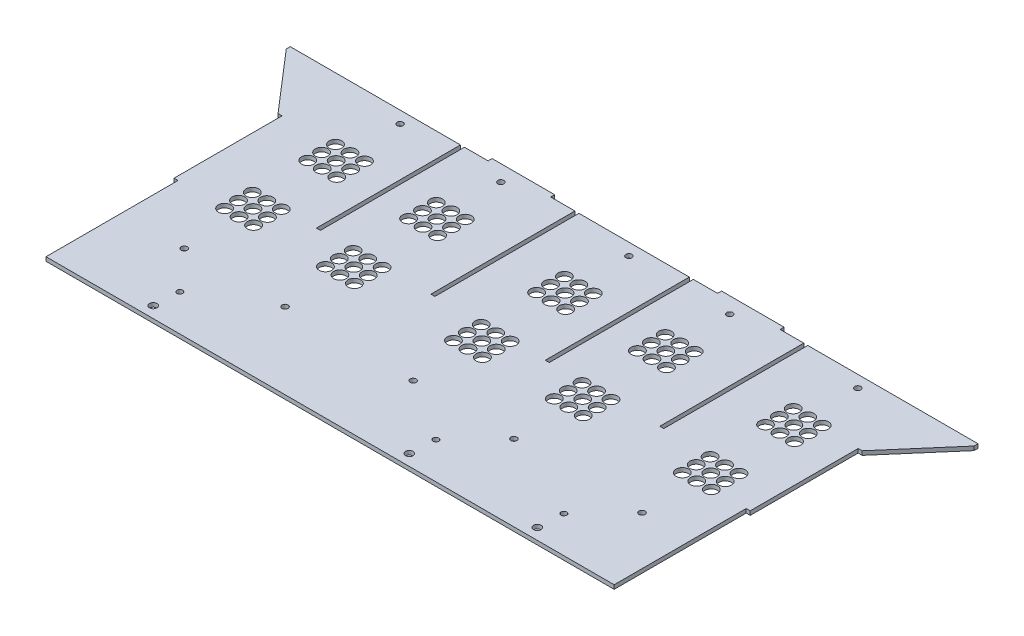
SolidWorks part; units mm, degrees
material "6061-T6 (SS)"
ref_plane "X-Y Datum" through (0, 0, 0) normal (0, 0, 1) x (1, 0, 0)
ref_plane "X-Z Datum" through (0, 0, 0) normal (0, 1, 0) x (1, 0, 0)
ref_plane "Y-Z Datum" through (0, 0, 0) normal (1, 0, 0) x (0, 0, -1)
sketch "Sketch1" plane through (0, 0, 0) normal (0, 0, 1) x (1, 0, 0)
  line L1 (-228.601, -1.5875) -> (228.601, -1.5875)
  line L2 (-228.601, -1.5875) -> (-228.601, 1.5875)
  line L3 (-228.601, 1.5875) -> (228.601, 1.5875)
  line L4 (228.601, -1.5875) -> (228.601, 1.5875)
  line L5 (-228.601, -1.5875) -> (228.601, 1.5875) construction
  line L6 (-228.601, 1.5875) -> (228.601, -1.5875) construction
  point P0 (0, 0)
  dimension "D1" = 3.175
  dimension "D2" = 457.202
extrude "Boss-Extrude1" add sketch "Sketch1" along normal blind 241.2744
sketch "Sketch2" plane through (0, 1.5875, 0) normal (0, 1, 0) x (1, 0, 0)
  line L0 (228.601, 0) -> (225.426, 0)
  line L1 (228.601, 0) -> (-228.601, 0) construction
  line L2 (225.426, 0) -> (137.796, 0)
  line L3 (137.796, 0) -> (134.621, 0)
  line L10 (134.621, 0) -> (137.796, 0)
  line L11 (134.621, 0) -> (134.621, -114.3)
  line L12 (134.621, -114.3) -> (137.796, -114.3)
  line L13 (137.796, 0) -> (137.796, -114.3)
  line M2 (228.601, 0) -> (-228.601, 0)
  dimension "D1" = 87.63
  dimension "D2" = 3.175
  dimension "D3" = 114.3
  dimension "D4" = 3.175
extrude "Cut-Extrude1" cut sketch "Sketch2" against normal through all contours L13 L11 L12 M2 region at (136.2085, 1.5875, 57.15)
pattern_linear "LPattern1" count 4 spacing 90.807 along (-1, 0, 0) of "Cut-Extrude1"
sketch "Sketch4" plane through (0, -1.5875, 0) normal (0, -1, 0) x (1, 0, 0)
  line L0 (-228.601, 0) -> (-272.876, 0)
  line L2 (-228.601, 241.2744) -> (-228.601, 0) construction
  line L3 (-228.601, 50.8) -> (-228.601, 0)
  line L4 (-272.876, 0) -> (-272.876, 3.175)
  line L6 (-228.601, 50.8) -> (-231.776, 50.8)
  line L7 (-231.776, 50.8) -> (-272.876, 3.175)
  dimension "D1" = 44.275
  dimension "D2" = 50.8
  dimension "D3" = 3.175
  dimension "D4" = 3.175
extrude "Boss-Extrude3" add sketch "Sketch4" against normal blind 3.175
mirror "Mirror1" about plane through (0, 0, 0) normal (1, 0, 0) of "Boss-Extrude3"
sketch "Sketch5" plane through (0, -1.5875, 0) normal (0, -1, 0) x (1, 0, 0)
  line L1 (-228.601, 241.2744) -> (-225.426, 241.2744)
  line L2 (-228.601, 241.2744) -> (-228.601, 136.4994)
  line L3 (-228.601, 136.4994) -> (-225.426, 136.4994)
  line L4 (-225.426, 241.2744) -> (-225.426, 136.4994)
  dimension "D1" = 3.175
  dimension "D2" = 104.775
extrude "Cut-Extrude2" cut sketch "Sketch5" against normal blind 3.175
mirror "Mirror2" about plane through (0, 0, 0) normal (1, 0, 0) of "Cut-Extrude2"
sketch "Sketch37" plane through (0, 1.5875, 0) normal (0, 1, 0) x (1, 0, 0)
  line L0 (-149.226, -241.2744) -> (-149.226, -232.3844) construction
  line L1 (225.426, -241.2744) -> (-225.426, -241.2744) construction
  line L2 (-225.426, -136.4994) -> (-225.426, -241.2744) construction
  circle A0 centre (-149.226, -232.3844) radius 3
  dimension "D1" = 8.89
  dimension "D3" = 6
  dimension "D2" = 76.2
extrude "Cut-Extrude12" cut sketch "Sketch37" against normal blind 3.175
pattern_linear "LPattern31" count 4 spacing 101.6 along (1, 0, 0) skipping (1, 0) of "Cut-Extrude12"
sketch "Sketch51" plane through (0, 1.5875, 0) normal (0, 1, 0) x (1, 0, 0)
  point P0 (-176.2216, -180.775)
  point P1 (-176.2216, -9.525)
  point P3 (-96.2064, -9.525)
  point P5 (-96.2064, -180.775)
hole_wizard "M4 Clearance Hole1" positions "Sketch55" profile "Sketch53" hole size "M4" standard "ANSI Metric" end condition up to next
sketch "Sketch55" plane through (0, 1.5875, 0) normal (0, 1, 0) x (1, 0, 0)
  point P0 (-176.2216, -180.775)
  point P3 (-176.2216, -9.525)
sketch "Sketch53" plane through (-176.2216, 1.5875, 180.775) normal (1, 0, 0) x (0, 0, 1)
  line L0 (0, 0) -> (0, 3.175)
  line L1 (0, 3.175) -> (2.4, 3.175)
  line L2 (2.4, 3.175) -> (2.4, 0)
  line L5 (2.4, 0) -> (0, 0)
  line L11 (0, -6.35) -> (0, 107.95) construction
  dimension "Thru Hole Dia." = 4.8
  dimension "Thru Hole Depth" = 3.175
hole_wizard "M4 Clearance Hole2" positions "Sketch58" profile "Sketch57" hole size "M4" standard "ANSI Metric" end condition up to next
sketch "Sketch58" plane through (0, 1.5875, 0) normal (0, 1, 0) x (1, 0, 0)
  point P0 (-96.2064, -180.775)
  point P3 (-96.2064, -9.525)
sketch "Sketch57" plane through (-96.2064, 1.5875, 180.775) normal (1, 0, 0) x (0, 0, 1)
  line L0 (0, 0) -> (0, 3.175)
  line L1 (0, 3.175) -> (2.4, 3.175)
  line L2 (2.4, 3.175) -> (2.4, 0)
  line L5 (2.4, 0) -> (0, 0)
  line L11 (0, -6.35) -> (0, 107.95) construction
  dimension "Thru Hole Dia." = 4.8
  dimension "Thru Hole Depth" = 3.175
pattern_linear "LPattern32" count 3 spacing 181.614 along (1, 0, 0) of "M4 Clearance Hole1"
pattern_linear "LPattern33" count 2 spacing 181.614 along (1, 0, 0) of "M4 Clearance Hole2"
sketch "Sketch59" plane through (0, 1.5875, 0) normal (0, 1, 0) x (1, 0, 0)
  circle A0 centre (-187.7216, -115.2567) radius 5 construction
  circle A1 centre (-176.2216, -115.2567) radius 5 construction
  circle A2 centre (-164.7216, -115.2567) radius 5 construction
  circle A3 centre (-164.7216, -126.2567) radius 5 construction
  circle A4 centre (-176.2216, -126.2567) radius 5 construction
  circle A5 centre (-187.7216, -126.2567) radius 5 construction
  circle A6 centre (-187.7216, -137.2567) radius 5 construction
  circle A7 centre (-176.2216, -137.2567) radius 5 construction
  circle A8 centre (-164.7216, -137.2567) radius 5 construction
  circle A9 centre (-187.7216, -115.2567) radius 5
  circle A10 centre (-176.2216, -115.2567) radius 5
  circle A11 centre (-164.7216, -115.2567) radius 5
  circle A12 centre (-164.7216, -126.2567) radius 5
  circle A13 centre (-176.2216, -126.2567) radius 5
  circle A14 centre (-187.7216, -126.2567) radius 5
  circle A15 centre (-187.7216, -137.2567) radius 5
  circle A16 centre (-176.2216, -137.2567) radius 5
  circle A17 centre (-164.7216, -137.2567) radius 5
  circle A18 centre (-187.7216, -71.2567) radius 5 construction
  circle A19 centre (-176.2216, -71.2567) radius 5 construction
  circle A20 centre (-164.7216, -71.2567) radius 5 construction
  circle A21 centre (-176.2216, -60.2567) radius 5 construction
  circle A22 centre (-187.7216, -60.2567) radius 5 construction
  circle A23 centre (-187.7216, -49.2567) radius 5 construction
  circle A24 centre (-176.2216, -49.2567) radius 5 construction
  circle A25 centre (-164.7216, -49.2567) radius 5 construction
  circle A26 centre (-164.7216, -60.2567) radius 5 construction
  circle A27 centre (-187.7216, -71.2567) radius 5
  circle A28 centre (-176.2216, -71.2567) radius 5
  circle A29 centre (-164.7216, -71.2567) radius 5
  circle A30 centre (-176.2216, -60.2567) radius 5
  circle A31 centre (-187.7216, -60.2567) radius 5
  circle A32 centre (-187.7216, -49.2567) radius 5
  circle A33 centre (-176.2216, -49.2567) radius 5
  circle A34 centre (-164.7216, -49.2567) radius 5
  circle A35 centre (-164.7216, -60.2567) radius 5
  circle A36 centre (-107.7064, -126.2567) radius 5 construction
  circle A37 centre (-107.7064, -115.2567) radius 5 construction
  circle A38 centre (-107.7064, -137.2567) radius 5 construction
  circle A39 centre (-96.2064, -137.2567) radius 5 construction
  circle A40 centre (-96.2064, -126.2567) radius 5 construction
  circle A41 centre (-96.2064, -115.2567) radius 5 construction
  circle A42 centre (-84.7064, -115.2567) radius 5 construction
  circle A43 centre (-84.7064, -126.2567) radius 5 construction
  circle A44 centre (-84.7064, -137.2567) radius 5 construction
  circle A45 centre (-107.7064, -126.2567) radius 5
  circle A46 centre (-107.7064, -115.2567) radius 5
  circle A47 centre (-107.7064, -137.2567) radius 5
  circle A48 centre (-96.2064, -137.2567) radius 5
  circle A49 centre (-96.2064, -126.2567) radius 5
  circle A50 centre (-96.2064, -115.2567) radius 5
  circle A51 centre (-84.7064, -115.2567) radius 5
  circle A52 centre (-84.7064, -126.2567) radius 5
  circle A53 centre (-84.7064, -137.2567) radius 5
  circle A54 centre (-84.7064, -49.2567) radius 5 construction
  circle A55 centre (-96.2064, -49.2567) radius 5 construction
  circle A56 centre (-107.7064, -49.2567) radius 5 construction
  circle A57 centre (-107.7064, -60.2567) radius 5 construction
  circle A58 centre (-107.7064, -71.2567) radius 5 construction
  circle A59 centre (-96.2064, -71.2567) radius 5 construction
  circle A60 centre (-96.2064, -60.2567) radius 5 construction
  circle A61 centre (-84.7064, -60.2567) radius 5 construction
  circle A62 centre (-84.7064, -71.2567) radius 5 construction
  circle A63 centre (-84.7064, -49.2567) radius 5
  circle A64 centre (-96.2064, -49.2567) radius 5
  circle A65 centre (-107.7064, -49.2567) radius 5
  circle A66 centre (-107.7064, -60.2567) radius 5
  circle A67 centre (-107.7064, -71.2567) radius 5
  circle A68 centre (-96.2064, -71.2567) radius 5
  circle A69 centre (-96.2064, -60.2567) radius 5
  circle A70 centre (-84.7064, -60.2567) radius 5
  circle A71 centre (-84.7064, -71.2567) radius 5
extrude "Cut-Extrude13" cut sketch "Sketch59" against normal through all contours A34 | A33 | A32 | A31 | A35 | A29 | A28 | A27 | A15 | A16 | A17 | A12 | A13 | A14 | A11 | A10 | A9 | A30 region at (-187.7216, 1.5875, 115.2567) region at (-176.2216, 1.5875, 115.2567) region at (-164.7216, 1.5875, 115.2567) region at (-164.7216, 1.5875, 126.2567) region at (-176.2216, 1.5875, 126.2567) region at (-187.7216, 1.5875, 126.2567) region at (-187.7216, 1.5875, 137.2567) region at (-176.2216, 1.5875, 137.2567) region at (-164.7216, 1.5875, 137.2567) region at (-187.7216, 1.5875, 71.2567) region at (-176.2216, 1.5875, 71.2567) region at (-164.7216, 1.5875, 71.2567) region at (-187.7216, 1.5875, 60.2567) region at (-187.7216, 1.5875, 49.2567) region at (-176.2216, 1.5875, 49.2567) region at (-164.7216, 1.5875, 49.2567) region at (-164.7216, 1.5875, 60.2567)
pattern_linear "LPattern34" count 3 spacing 181.614 along (1, 0, 0) of "Cut-Extrude13"
sketch "Sketch60" plane through (0, 1.5875, 0) normal (0, 1, 0) x (1, 0, 0)
  circle A1 centre (-164.7216, -137.2567) radius 5
  circle A2 centre (-164.7216, -137.2567) radius 5
  circle A3 centre (-176.2216, -137.2567) radius 5
  circle A4 centre (-176.2216, -137.2567) radius 5
  circle A5 centre (-187.7216, -137.2567) radius 5
  circle A6 centre (-187.7216, -137.2567) radius 5
  circle A7 centre (-187.7216, -126.2567) radius 5
  circle A8 centre (-187.7216, -126.2567) radius 5
  circle A9 centre (-176.2216, -126.2567) radius 5
  circle A10 centre (-176.2216, -126.2567) radius 5
  circle A11 centre (-164.7216, -126.2567) radius 5
  circle A12 centre (-164.7216, -126.2567) radius 5
  circle A13 centre (-164.7216, -115.2567) radius 5
  circle A14 centre (-164.7216, -115.2567) radius 5
  circle A15 centre (-176.2216, -115.2567) radius 5
  circle A16 centre (-176.2216, -115.2567) radius 5
  circle A17 centre (-187.7216, -115.2567) radius 5
  circle A18 centre (-187.7216, -115.2567) radius 5
  circle A19 centre (-164.7216, -71.2567) radius 5
  circle A20 centre (-164.7216, -71.2567) radius 5
  circle A21 centre (-176.2216, -71.2567) radius 5
  circle A22 centre (-176.2216, -71.2567) radius 5
  circle A23 centre (-187.7216, -71.2567) radius 5
  circle A24 centre (-187.7216, -71.2567) radius 5
  circle A25 centre (-164.7216, -60.2567) radius 5
  circle A26 centre (-164.7216, -60.2567) radius 5
  circle A27 centre (-164.7216, -49.2567) radius 5
  circle A28 centre (-164.7216, -49.2567) radius 5
  circle A29 centre (-176.2216, -49.2567) radius 5
  circle A30 centre (-176.2216, -49.2567) radius 5
  circle A31 centre (-187.7216, -49.2567) radius 5
  circle A32 centre (-187.7216, -49.2567) radius 5
  circle A33 centre (-187.7216, -60.2567) radius 5
  circle A34 centre (-187.7216, -60.2567) radius 5
  circle A35 centre (-176.2216, -60.2567) radius 5
  circle A36 centre (-176.2216, -60.2567) radius 5
  circle A37 centre (-84.7064, -126.2567) radius 5
  circle A38 centre (-84.7064, -126.2567) radius 5
  circle A39 centre (-84.7064, -115.2567) radius 5
  circle A40 centre (-84.7064, -115.2567) radius 5
  circle A41 centre (-96.2064, -115.2567) radius 5
  circle A42 centre (-96.2064, -115.2567) radius 5
  circle A43 centre (-96.2064, -126.2567) radius 5
  circle A44 centre (-96.2064, -126.2567) radius 5
  circle A45 centre (-96.2064, -137.2567) radius 5
  circle A46 centre (-96.2064, -137.2567) radius 5
  circle A47 centre (-107.7064, -137.2567) radius 5
  circle A48 centre (-107.7064, -137.2567) radius 5
  circle A49 centre (-107.7064, -115.2567) radius 5
  circle A50 centre (-107.7064, -115.2567) radius 5
  circle A51 centre (-107.7064, -126.2567) radius 5
  circle A52 centre (-107.7064, -126.2567) radius 5
  circle A53 centre (-84.7064, -137.2567) radius 5
  circle A54 centre (-84.7064, -137.2567) radius 5
  circle A55 centre (-84.7064, -71.2567) radius 5
  circle A56 centre (-84.7064, -71.2567) radius 5
  circle A57 centre (-84.7064, -60.2567) radius 5
  circle A58 centre (-84.7064, -60.2567) radius 5
  circle A59 centre (-96.2064, -60.2567) radius 5
  circle A60 centre (-96.2064, -60.2567) radius 5
  circle A61 centre (-96.2064, -71.2567) radius 5
  circle A62 centre (-96.2064, -71.2567) radius 5
  circle A63 centre (-107.7064, -71.2567) radius 5
  circle A64 centre (-107.7064, -71.2567) radius 5
  circle A65 centre (-107.7064, -60.2567) radius 5
  circle A66 centre (-107.7064, -60.2567) radius 5
  circle A67 centre (-107.7064, -49.2567) radius 5
  circle A68 centre (-107.7064, -49.2567) radius 5
  circle A69 centre (-96.2064, -49.2567) radius 5
  circle A70 centre (-96.2064, -49.2567) radius 5
  circle A71 centre (-84.7064, -49.2567) radius 5
  circle A72 centre (-84.7064, -49.2567) radius 5
  dimension "D1" = 0
  dimension "D2" = 0
  dimension "D3" = 0
  dimension "D4" = 0
  dimension "D5" = 0
  dimension "D6" = 0
  dimension "D7" = 0
  dimension "D8" = 0
  dimension "D9" = 0
  dimension "D10" = 0
  dimension "D11" = 0
  dimension "D12" = 0
  dimension "D13" = 0
  dimension "D14" = 0
  dimension "D15" = 0
  dimension "D16" = 0
  dimension "D17" = 0
  dimension "D18" = 0
  dimension "D19" = 0
  dimension "D20" = 0
  dimension "D21" = 0
  dimension "D22" = 0
  dimension "D23" = 0
  dimension "D24" = 0
  dimension "D25" = 0
  dimension "D26" = 0
  dimension "D27" = 0
  dimension "D28" = 0
  dimension "D29" = 0
  dimension "D30" = 0
  dimension "D31" = 0
  dimension "D32" = 0
  dimension "D33" = 0
  dimension "D34" = 0
  dimension "D35" = 0
  dimension "D36" = 0
extrude "Cut-Extrude14" cut sketch "Sketch60" against normal through all contours A48 | A46 | A54 | A38 | A52 | A44 | A40 | A42 | A50 | A72 | A58 | A60 | A70 | A68 | A64 | A66 | A62 | A56
pattern_linear "LPattern35" count 2 spacing 181.614 along (1, 0, 0) of "Cut-Extrude14"
sketch "Sketch61" plane through (0, 1.5875, 0) normal (0, 1, 0) x (1, 0, 0)
  point P0 (-148.21, -212.285)
  point P1 (54.99, -212.285)
  point P3 (156.59, -212.285)
hole_wizard "M4 Clearance Hole3" positions "Sketch61" profile "Sketch62" hole size "M4" standard "ANSI Metric" end condition through all
sketch "Sketch62" plane through (-148.21, 1.5875, 212.285) normal (1, 0, 0) x (0, 0, 1)
  line L0 (0, 0) -> (0, 3.175)
  line L1 (0, 3.175) -> (2.25, 3.175)
  line L2 (2.25, 3.175) -> (2.25, 0)
  line L5 (2.25, 0) -> (0, 0)
  line L11 (0, -6.35) -> (0, 107.95) construction
  dimension "Thru Hole Dia." = 4.5
  dimension "Thru Hole Depth" = 3.175
sketch "Sketch63" plane through (0, 0, 0) normal (0, 0, -1) x (-1, 0, 0)
  line L0 (-66.1907, 1.5875) -> (-66.1907, -1.5875) construction
  line L1 (-115.8495, 1.5875) -> (-115.8495, -1.5875) construction
  line L2 (-115.8495, -1.5875) -> (-66.1907, -1.5875) construction
  line L3 (-66.1907, 1.5875) -> (-66.1907, -1.5875)
  line L4 (-115.8495, 1.5875) -> (-115.8495, -1.5875)
  line L5 (-115.8495, -1.5875) -> (-66.1907, -1.5875)
  line L6 (-228.1875, 1.7703) -> (228.1875, 1.7703) construction
  line L7 (-228.1875, 1.7703) -> (228.1875, 1.7703)
  line L8 (115.8495, 1.5875) -> (115.8495, -1.5875) construction
  line L9 (66.1907, 1.5875) -> (66.1907, -1.5875) construction
  line L10 (115.8495, -1.5875) -> (66.1907, -1.5875) construction
  line L11 (115.8495, 1.5875) -> (115.8495, -1.5875)
  line L12 (66.1907, 1.5875) -> (66.1907, -1.5875)
  line L13 (115.8495, -1.5875) -> (66.1907, -1.5875)
  line L14 (46.993, 1.5875) -> (134.625, 1.5875) construction
  line L15 (46.993, 1.5875) -> (134.625, 1.5875)
  line M1 (-134.621, -1.5875) -> (-46.989, -1.5875)
  line M3 (-46.989, 1.5875) -> (-134.621, 1.5875)
extrude "Boss-Extrude4" add sketch "Sketch63" along normal blind 3.175 contours L15 L12 L13 L11 | L4 L3 M3 M1 region at (91.0201, 0, 0) region at (-91.0201, 0, 0)
